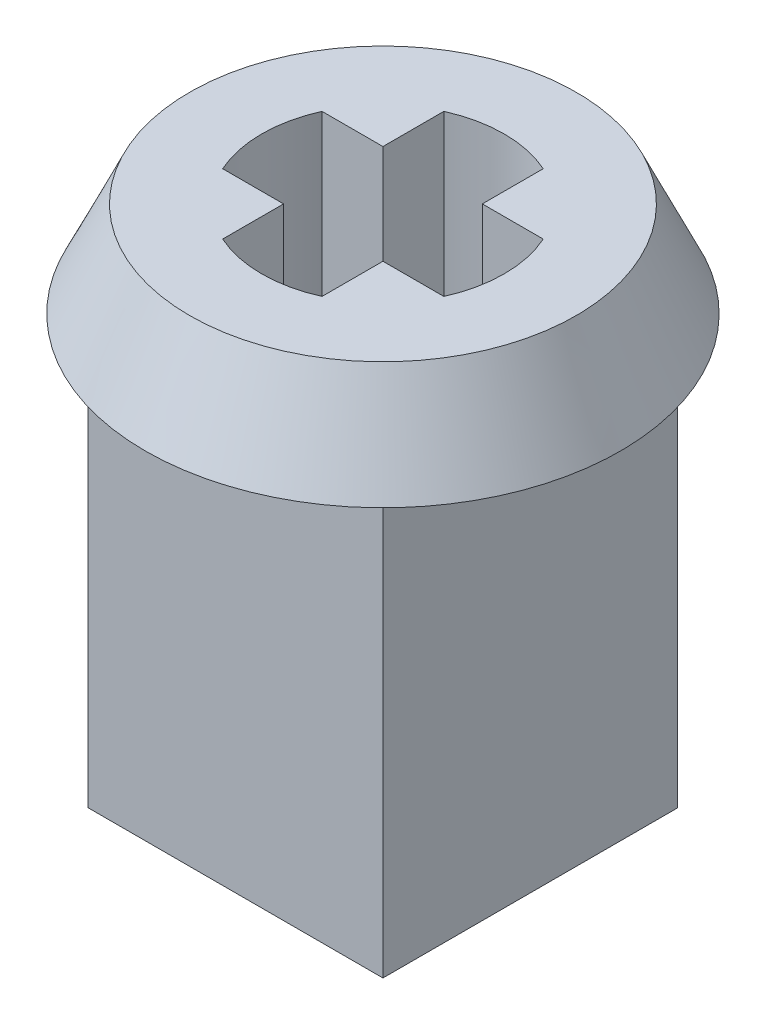
SolidWorks part; units mm, degrees
ref_plane "Front Plane" through (0, 0, 0) normal (0, 0, 1) x (1, 0, 0)
ref_plane "Top Plane" through (0, 0, 0) normal (0, 1, 0) x (1, 0, 0)
ref_plane "Right Plane" through (0, 0, 0) normal (1, 0, 0) x (0, 0, -1)
sketch "Sketch1" plane through (0, 0, 0) normal (0, 1, 0) x (1, 0, 0)
  line L1 (-3.1, -3.1) -> (3.1, -3.1)
  line L2 (-3.1, -3.1) -> (-3.1, 3.1)
  line L3 (-3.1, 3.1) -> (3.1, 3.1)
  line L4 (3.1, -3.1) -> (3.1, 3.1)
  line L5 (-3.1, -3.1) -> (3.1, 3.1) construction
  line L6 (-3.1, 3.1) -> (3.1, -3.1) construction
  point P0 (0, 0)
  dimension "D1" = 6.2
extrude "Boss-Extrude1" add sketch "Sketch1" along normal blind 9
sketch "Sketch2" plane through (0, 9, 0) normal (0, 1, 0) x (1, 0, 0)
  circle A0 centre (0, 0) radius 5
  dimension "D1" = 10
extrude "Boss-Extrude2" add sketch "Sketch2" along normal blind 2
sketch "Sketch3" plane through (0, 0, 0) normal (0, -1, 0) x (-1, 0, 0)
  line L0 (1.045, -2.326) -> (1.045, 2.326)
  line L1 (-1.045, -2.326) -> (-1.045, 2.326)
  line L2 (-2.6, -2.6) -> (35352.7391, 35352.7391) construction
  line L3 (-2.326, -1.045) -> (2.326, -1.045)
  line L4 (-2.326, 1.045) -> (2.326, 1.045)
  circle A0 centre (0, 0) radius 2.55
  dimension "D1" = 5.1
  dimension "D2" = 2.09
extrude "Cut-Extrude1" cut sketch "Sketch3" against normal up to next contours L1 A0 L0 L3 | L3 A0 L4 L0 | L2 L3 L0 | L1 L2 L4 | L4 A0 L3 L1 | L0 A0 L1 L4 region at (0, 0, 1.7624) region at (-0.3483, 0, 0.3483) region at (-1.7624, 0, 0) region at (0, 0, -1.7624) region at (0.3483, 0, -0.3483) region at (1.7624, 0, 0)
chamfer "Chamfer1" distance 2 angle 25 1 edges at (0, 11, 5) first distance on face at (0, 11, 5)
